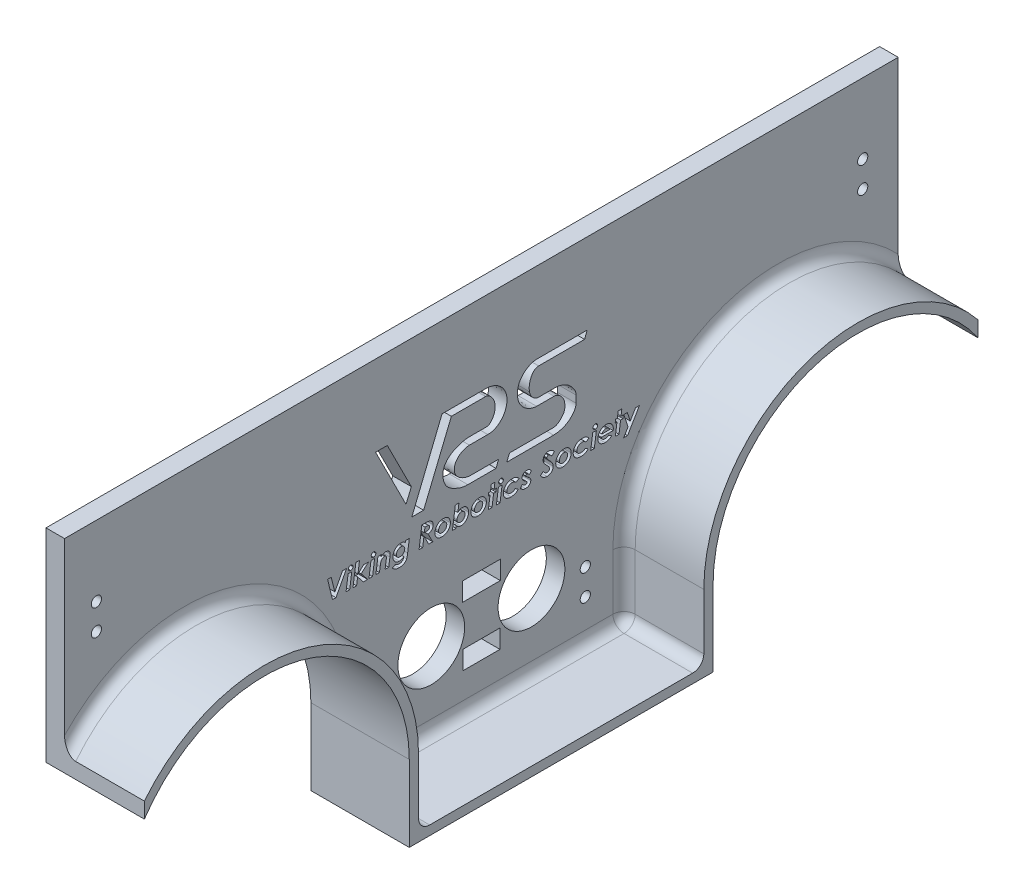
SolidWorks part; units mm, degrees
ref_plane "Front" through (0, 0, 0) normal (0, 0, 1) x (1, 0, 0)
ref_plane "Top" through (0, 0, 0) normal (0, 1, 0) x (1, 0, 0)
ref_plane "Right" through (0, 0, 0) normal (1, 0, 0) x (0, 0, -1)
sketch "wheelArchesSketch" plane through (0, 0, 0) normal (1, 0, 0) x (0, 0, -1)
  line L0 (112.295, 7.5) -> (112.295, 0) construction
  line L1 (0, 0) -> (224.59, 0) construction
  line L2 (0, 0) -> (0, 7.5) construction
  line L3 (0, 7.5) -> (224.59, 7.5) construction
  line L4 (224.59, 0) -> (224.59, 7.5) construction
  line L5 (71.3676, 20.5282) -> (71.3676, 0)
  line L6 (153.2224, 20.5282) -> (153.2224, 0)
  line L7 (73.8676, 20.5282) -> (73.8676, 0)
  line L8 (0, 42.2846) -> (0, 46.5011)
  line L9 (150.7224, 20.5282) -> (150.7224, 0)
  line L10 (224.59, 42.2846) -> (224.59, 46.5011)
  line L12 (150.7224, 0) -> (153.2224, 0)
  line L13 (71.3676, 0) -> (73.8676, 0)
  arc A1 (0, 42.2846) -> (71.3676, 20.5282) centre (32.3676, 20.5282) cw
  arc A2 (224.59, 42.2846) -> (153.2224, 20.5282) centre (192.2224, 20.5282) ccw
  arc A3 (0, 46.5011) -> (73.8676, 20.5282) centre (32.3676, 20.5282) cw
  arc A4 (-2.0748, 43.6792) -> (73.8676, 20.5282) centre (32.3676, 20.5282) cw construction
  arc A5 (224.59, 46.5011) -> (150.7224, 20.5282) centre (192.2224, 20.5282) ccw
  point P5 (32.3676, 20.5282)
  dimension "D5" = 39
  dimension "D1" = 224.59
  dimension "D2" = 7.5
  dimension "D3" = 32.3676
  dimension "D4" = 13.0282
  dimension "D6" = 2.5
extrude "wheelArches" add sketch "wheelArchesSketch" along normal blind 26.5
sketch "Sketch3" plane through (0, 0, 0) normal (1, 0, 0) x (0, 0, -1)
  line L0 (0, 46.5011) -> (0, 42.2846) construction
  line L1 (71.3676, 0) -> (153.2224, 0)
  line L2 (0, 42.2846) -> (0, 87)
  line L3 (0, 87) -> (224.59, 87)
  line L4 (224.59, 42.2846) -> (224.59, 87)
  line L6 (224.59, 42.2846) -> (224.59, 46.5011) construction
  line L7 (71.3676, 0) -> (73.8676, 0) construction
  line L8 (71.3676, 20.5282) -> (71.3676, 0) construction
  line L9 (71.3676, 20.5282) -> (71.3676, 0)
  line L10 (153.2224, 0) -> (153.2224, 20.5282) construction
  line L11 (153.2224, 0) -> (153.2224, 20.5282)
  arc A0 (71.3676, 20.5282) -> (0, 42.2846) centre (32.3676, 20.5282) ccw construction
  arc A1 (71.3676, 20.5282) -> (0, 42.2846) centre (32.3676, 20.5282) ccw
  arc A2 (224.59, 42.2846) -> (153.2224, 20.5282) centre (192.2224, 20.5282) ccw construction
  arc A3 (224.59, 42.2846) -> (153.2224, 20.5282) centre (192.2224, 20.5282) ccw
  dimension "D1" = 87
extrude "sideWall" add sketch "Sketch3" along normal blind 2.5
sketch "Sketch4" plane through (2.5, 0, 0) normal (1, 0, 0) x (0, 0, -1)
  line L0 (150.7224, 0) -> (150.7224, 20.5282) construction
  line L1 (73.8676, 0) -> (150.7224, 0) construction
  line L2 (73.8676, 0) -> (73.8676, 7.5) construction
  line L3 (73.8676, 7.5) -> (150.7224, 7.5) construction
  line L4 (150.7224, 0) -> (150.7224, 7.5) construction
  line L5 (112.295, 7.5) -> (112.295, 37) construction
  line L6 (87.295, 7.5) -> (137.295, 7.5) construction
  line L7 (87.295, 7.5) -> (87.295, 37) construction
  line L8 (87.295, 37) -> (137.295, 37) construction
  line L9 (137.295, 7.5) -> (137.295, 37) construction
  circle A0 centre (98.795, 22.5) radius 9
  circle A1 centre (90.9643, 31.289) radius 0.875
  circle A2 centre (90.9643, 13.711) radius 0.875
  circle A3 centre (133.6257, 13.711) radius 0.875
  circle A4 centre (133.6257, 31.289) radius 0.875
  circle A5 centre (125.795, 22.5) radius 9
  point P11 (112.295, 7.5)
  point P12 (112.295, 7.5)
  dimension "D4" = 18
  dimension "D7" = 1.75
  dimension "D1" = 7.5
  dimension "D2" = 29.5
  dimension "D3" = 50
  dimension "D5" = 5.711
  dimension "D6" = 3.6693
  dimension "D8" = 6.211
  dimension "D9" = 3.6693
  dimension "D10" = 15
  dimension "D11" = 11.5
extrude "distanceSensorMountingHoles1" cut sketch "Sketch4" against normal blind 10
sketch "Sketch5" plane through (2.5, 0, 0) normal (1, 0, 0) x (0, 0, -1)
  circle A0 centre (90.9643, 31.289) radius 1.25
  circle A1 centre (90.9643, 13.711) radius 1.25
  circle A2 centre (133.6257, 13.711) radius 1.25
  circle A3 centre (133.6257, 31.289) radius 1.25
  dimension "D1" = 2.5
extrude "distanceSensorMountingHoles2" cut sketch "Sketch5" against normal offset from surface (1.5 mm away) 1 up to face at (0, 31.289, -90.0893)
sketch "Sketch6" plane through (0, 87, 0) normal (0, 1, 0) x (1, 0, 0)
  line L4 (0, 224.59) -> (0, 0)
  line L5 (0, 0) -> (2.5, 0)
  line L6 (2.5, 0) -> (2.5, 224.59)
  line L7 (2.5, 224.59) -> (0, 224.59)
  line L8 (0, 224.59) -> (0, 0)
  line L9 (0, 0) -> (2.5, 0)
  line L10 (2.5, 0) -> (2.5, 224.59)
  line L11 (2.5, 224.59) -> (0, 224.59)
  dimension "D1" = 0
extrude "wallExtension" add sketch "Sketch6" along normal blind 5
ref_plane "referencePlane1" through (0, 87, 0) normal (0, 1, 0) x (1, 0, 0)
sketch "Sketch7" plane through (0, 87, 0) normal (0, 1, 0) x (1, 0, 0)
  line L0 (0, 112.295) -> (-12.5, 112.295) construction
  line L1 (0, 224.59) -> (0, 0) construction
  line L2 (0, 207.455) -> (-12.5, 207.455)
  line L3 (0, 0) -> (-12.5, 0)
  line L4 (0, 0) -> (0, 17.135)
  line L5 (0, 17.135) -> (-12.5, 17.135)
  line L6 (-12.5, 0) -> (-12.5, 17.135)
  line L7 (-12.5, 224.59) -> (-12.5, 207.455)
  line L8 (0, 224.59) -> (-12.5, 224.59)
  line L9 (0, 224.59) -> (0, 207.455)
  dimension "D1" = 17.135
  dimension "D2" = 12.5
extrude "topChassisMountingTabs" add sketch "Sketch7" against normal blind 5
sketch "Sketch8" plane through (0, 87, 0) normal (0, 1, 0) x (1, 0, 0)
  line L0 (0, 112.295) -> (-12.8293, 112.295) construction
  line L1 (0, 224.59) -> (0, 0) construction
  line L2 (-6.25, 0) -> (-6.25, 17.135) construction
  line L3 (-12.5, 0) -> (0, 0) construction
  line L4 (0, 17.135) -> (-12.5, 17.135) construction
  circle A0 centre (-6.25, 8.5675) radius 1.375
  circle A1 centre (-6.25, 216.0225) radius 1.375
  dimension "D1" = 2.75
extrude "topChassisMountingHoles" cut sketch "Sketch8" against normal blind 5
ref_plane "referencePlane2" through (0, 7.5, 0) normal (0, -1, 0) x (-1, 0, 0)
sketch "Sketch9" plane through (0, 7.5, 0) normal (0, -1, 0) x (-1, 0, 0)
  line L0 (0, 224.59) -> (0, 0) construction
  line L1 (0, 87.295) -> (12.5, 87.295)
  line L2 (0, 87.295) -> (0, 137.295)
  line L3 (0, 137.295) -> (12.5, 137.295)
  line L4 (12.5, 87.295) -> (12.5, 137.295)
  point P4 (0, 112.295)
  point P7 (0, 112.295)
  dimension "D1" = 12.5
  dimension "D2" = 50
extrude "bottomTab" add sketch "Sketch9" against normal blind 1.75
sketch "Sketch10" plane through (0, 9.25, 0) normal (0, 1, 0) x (1, 0, 0)
  line L0 (-12.5, 112.295) -> (0, 112.295) construction
  line L1 (-12.5, 87.295) -> (-12.5, 137.295) construction
  line L2 (0, 137.295) -> (0, 87.295) construction
  line L3 (0, 87.295) -> (-12.5, 87.295) construction
  circle A0 centre (-9.75, 90.295) radius 1.375
  circle A1 centre (-9.75, 134.295) radius 1.375
  dimension "D1" = 2.75
  dimension "D2" = 3
  dimension "D3" = 2.75
extrude "bottomTabMountingHoles" cut sketch "Sketch10" against normal blind 1.75
sketch "Sketch11" plane through (0, 92, 0) normal (0, 1, 0) x (1, 0, 0)
  line L4 (2.5, 224.59) -> (0, 224.59)
  line L5 (0, 224.59) -> (0, 0)
  line L6 (0, 0) -> (2.5, 0)
  line L7 (2.5, 0) -> (2.5, 224.59)
  line L8 (2.5, 224.59) -> (0, 224.59)
  line L9 (0, 224.59) -> (0, 0)
  line L10 (0, 0) -> (2.5, 0)
  line L11 (2.5, 0) -> (2.5, 224.59)
  dimension "D1" = 0
extrude "Boss-Extrude1" add sketch "Sketch11" along normal blind 5
sketch "Sketch12" plane through (2.5, 0, 0) normal (1, 0, 0) x (0, 0, -1)
  line L6 (150.7224, 0) -> (150.7224, 20.5282)
  line L7 (224.59, 46.5011) -> (224.59, 97)
  line L8 (224.59, 97) -> (0, 97)
  line L9 (0, 97) -> (0, 46.5011)
  line L10 (73.8676, 20.5282) -> (73.8676, 0)
  line L11 (73.8676, 0) -> (150.7224, 0)
  line L12 (150.7224, 0) -> (150.7224, 20.5282)
  line L13 (224.59, 46.5011) -> (224.59, 97)
  line L14 (224.59, 97) -> (0, 97)
  line L15 (0, 97) -> (0, 46.5011)
  line L16 (73.8676, 20.5282) -> (73.8676, 0)
  line L17 (73.8676, 0) -> (150.7224, 0)
  circle A0 centre (90.9643, 13.711) radius 0.875 construction
  circle A1 centre (133.6257, 13.711) radius 0.875 construction
  arc A2 (224.59, 46.5011) -> (150.7224, 20.5282) centre (192.2224, 20.5282) ccw
  arc A3 (73.8676, 20.5282) -> (0, 46.5011) centre (32.3676, 20.5282) ccw
  arc A4 (224.59, 46.5011) -> (150.7224, 20.5282) centre (192.2224, 20.5282) ccw
  arc A5 (73.8676, 20.5282) -> (0, 46.5011) centre (32.3676, 20.5282) ccw
  circle A6 centre (133.6257, 31.289) radius 0.875 construction
  circle A7 centre (90.9643, 31.289) radius 0.875 construction
  circle A8 centre (90.9643, 13.711) radius 0.875
  circle A9 centre (133.6257, 13.711) radius 0.875
  circle A10 centre (133.6257, 31.289) radius 0.875
  circle A11 centre (90.9643, 31.289) radius 0.875
  dimension "D1" = 0
extrude "Boss-Extrude2" add sketch "Sketch12" along normal blind 2.5
sketch "Sketch13" plane through (1, 0, 0) normal (1, 0, 0) x (0, 0, -1)
  circle A0 centre (90.9643, 31.289) radius 1.25 construction
  circle A1 centre (90.9643, 31.289) radius 1.25
  circle A2 centre (133.6257, 13.711) radius 1.25 construction
  circle A3 centre (133.6257, 13.711) radius 1.25
  circle A4 centre (90.9643, 13.711) radius 1.25 construction
  circle A5 centre (90.9643, 13.711) radius 1.25
  circle A6 centre (133.6257, 31.289) radius 1.25 construction
  circle A7 centre (133.6257, 31.289) radius 1.25
extrude "Cut-Extrude1" cut sketch "Sketch13" along normal through all
sketch "Sketch14" plane through (2.5, 0, 0) normal (-1, 0, 0) x (0, 0, 1)
  circle A1 centre (-125.795, 22.5) radius 9
  circle A2 centre (-125.795, 22.5) radius 9
  circle A3 centre (-98.795, 22.5) radius 9
  circle A4 centre (-98.795, 22.5) radius 9
  dimension "D1" = 0
  dimension "D2" = 0
extrude "Cut-Extrude2" cut sketch "Sketch14" against normal blind 10
sketch "Sketch15" plane through (5, 0, 0) normal (1, 0, 0) x (0, 0, -1)
  line L0 (98.795, 13.5) -> (98.795, 31.5) construction
  line L1 (89.795, 22.5) -> (107.795, 22.5) construction
  line L3 (107.295, 17.5) -> (117.295, 17.5)
  line L4 (107.295, 17.5) -> (107.295, 12.5)
  line L5 (107.295, 12.5) -> (117.295, 12.5)
  line L6 (117.295, 17.5) -> (117.295, 12.5)
  line L7 (107.185, 33.5) -> (117.405, 33.5)
  line L8 (107.185, 33.5) -> (107.185, 28.5)
  line L9 (107.185, 28.5) -> (117.405, 28.5)
  line L10 (117.405, 33.5) -> (117.405, 28.5)
  circle A0 centre (98.795, 22.5) radius 9 construction
  circle A1 centre (98.795, 22.5) radius 9 construction
  point P24 (107.185, 31)
  dimension "D1" = 5
  dimension "D2" = 10
  dimension "D3" = 8.5
  dimension "D4" = 5
  dimension "D5" = 5
  dimension "D6" = 10.22
  dimension "D7" = 8.39
  dimension "D8" = 8.5
extrude "Cut-Extrude3" cut sketch "Sketch15" against normal blind 10
sketch "Sketch16" plane through (0, 87, 0) normal (0, 1, 0) x (1, 0, 0)
  line L0 (0, 224.59) -> (0, 0) construction
  line L1 (-12.5, 0) -> (0, 0)
  line L2 (-12.5, 0) -> (-12.5, 2)
  line L3 (-12.5, 2) -> (0, 2)
  line L4 (0, 0) -> (0, 2)
  dimension "D1" = 2
extrude "Cut-Extrude4" cut sketch "Sketch16" against normal blind 10
sketch "Sketch17" plane through (5, 0, 0) normal (1, 0, 0) x (0, 0, -1)
  line L0 (150.7224, 20.5282) -> (150.7224, 0) construction
  line L1 (73.8676, 0) -> (150.7224, 0)
  line L2 (73.8676, 0) -> (73.8676, 2.5)
  line L3 (73.8676, 2.5) -> (150.7224, 2.5)
  line L4 (150.7224, 0) -> (150.7224, 2.5)
  dimension "D1" = 2.5
extrude "Boss-Extrude3" add sketch "Sketch17" along normal up to surface (21.5 mm away) up to face at (26.5, 30.4055, -51.2877)
fillet "Fillet1" radius 3 7 edges at (5, 11.5141, -150.7224) (5, 11.5141, -73.8676) (5, 59.6786, -178.4566) (5, 2.5, -112.295) (5, 59.6786, -46.1334) (15.75, 2.5, -150.7224) (15.75, 2.5, -73.8676)
sketch "Sketch18" plane through (0, 0, 0) normal (-1, 0, 0) x (0, 0, 1)
  line L0 (-112.295, 0) -> (-112.295, 97) construction
  line L6 (-224.59, 51.0665) -> (-224.59, 97) construction
  line L11 (-71.3676, 0) -> (-153.2224, 0) construction
  line L12 (-224.59, 97) -> (0, 97) construction
  line L13 (0, 97) -> (0, 51.0665) construction
  line L14 (-206.455, 82.0153) -> (-223.59, 82.0153) construction
  line L15 (-206.455, 82.0153) -> (-206.455, 67.0153) construction
  line L16 (-206.455, 67.0153) -> (-223.59, 67.0153) construction
  line L17 (-223.59, 82.0153) -> (-223.59, 67.0153) construction
  circle A6 centre (-215.0225, 78.0153) radius 1.375
  circle A7 centre (-215.0225, 71.0153) radius 1.375
  circle A12 centre (-8.5675, 78.0153) radius 1.375
  circle A13 centre (-8.5675, 71.0153) radius 1.375
  point P11 (-215.0225, 82.0153)
  dimension "D2" = 1
  dimension "D7" = 4
  dimension "D5" = 2.75
  dimension "D3" = 15
  dimension "D4" = 18.9847
  dimension "D6" = 7
  dimension "D8" = 8.5675
  dimension "D11" = 9.5675
extrude "Cut-Extrude5" cut sketch "Sketch18" against normal blind 10
sketch "Sketch19" plane through (0, 87, 0) normal (0, 1, 0) x (1, 0, 0)
  line L1 (-12.5, 17.135) -> (0, 17.135)
  line L2 (-12.5, 17.135) -> (-12.5, 2)
  line L3 (-12.5, 2) -> (0, 2)
  line L4 (0, 17.135) -> (0, 2)
  line L5 (-12.5, 224.59) -> (0, 224.59)
  line L6 (-12.5, 224.59) -> (-12.5, 207.455)
  line L7 (-12.5, 207.455) -> (0, 207.455)
  line L8 (0, 224.59) -> (0, 207.455)
extrude "Cut-Extrude6" cut sketch "Sketch19" against normal blind 10
sketch "Sketch20" plane through (0, 0, 0) normal (-1, 0, 0) x (0, 0, 1)
  line L0 (-112.295, 9.25) -> (-112.295, 33.5) construction
  line L1 (-137.295, 9.25) -> (-87.295, 9.25) construction
  line L2 (-107.185, 33.5) -> (-117.405, 33.5) construction
  circle A0 centre (-140.295, 20.25) radius 1.375
  circle A1 centre (-140.295, 13.25) radius 1.375
  circle A2 centre (-84.295, 13.25) radius 1.375
  circle A3 centre (-84.295, 20.25) radius 1.375
  dimension "D1" = 2.75
  dimension "D2" = 7
  dimension "D3" = 3
  dimension "D4" = 4
extrude "Cut-Extrude7" cut sketch "Sketch20" against normal blind 10
sketch "Sketch21" plane through (0, 9.25, 0) normal (0, 1, 0) x (1, 0, 0)
  line L4 (0, 87.295) -> (0, 137.295)
  line L5 (0, 137.295) -> (-12.5, 137.295)
  line L6 (-12.5, 137.295) -> (-12.5, 87.295)
  line L7 (-12.5, 87.295) -> (0, 87.295)
  line L8 (0, 87.295) -> (0, 137.295)
  line L9 (0, 137.295) -> (-12.5, 137.295)
  line L10 (-12.5, 137.295) -> (-12.5, 87.295)
  line L11 (-12.5, 87.295) -> (0, 87.295)
  dimension "D1" = 0
extrude "Cut-Extrude8" cut sketch "Sketch21" against normal blind 10
sketch "Sketch22" plane through (5, 0, 0) normal (1, 0, 0) x (0, 0, -1)
  circle A0 centre (90.9643, 31.289) radius 1.25
  circle A1 centre (90.9643, 13.711) radius 1.25
  circle A2 centre (133.6257, 13.711) radius 1.25
  circle A3 centre (133.6257, 31.289) radius 1.25
  circle A5 centre (90.9643, 31.289) radius 1.25 construction
  circle A6 centre (90.9643, 13.711) radius 1.25 construction
  circle A7 centre (133.6257, 31.289) radius 1.25 construction
  circle A8 centre (133.6257, 13.711) radius 1.25 construction
extrude "Boss-Extrude4" add sketch "Sketch22" against normal up to surface (5 mm away) up to face at (0, 46.5599, -112.295)
sketch "Sketch24" plane through (5, 0, 0) normal (1, 0, 0) x (0, 0, -1)
  line L0 (147.5058, 113.6649) -> (400.1724, 113.6649) construction
sketch "vrs logo sketch 1" plane through (5, 0, 0) normal (1, 0, 0) x (0, 0, -1)
  line L0 (83.795, 75.25) -> (91.9924, 58.9987)
  line L1 (83.795, 55.25) -> (140.795, 55.25) construction
  line L2 (83.795, 55.25) -> (83.795, 75.25) construction
  line L3 (83.795, 75.25) -> (140.795, 75.25) construction
  line L4 (140.795, 55.25) -> (140.795, 75.25) construction
  line L5 (91.9924, 58.9987) -> (93.4297, 62.4001)
  line L6 (93.4297, 62.4001) -> (86.948, 75.25)
  line L7 (83.795, 75.25) -> (86.948, 75.25)
  line L8 (93.5622, 55.25) -> (101.6971, 75.25)
  line L9 (93.5622, 55.25) -> (96.7347, 55.25)
  line L10 (96.7347, 55.25) -> (104.2097, 73.4229)
  line L11 (104.2097, 73.4229) -> (113.4267, 73.4229)
  line L12 (101.6971, 75.25) -> (113.4267, 75.25)
  line L14 (113.6549, 66.2225) -> (109.0786, 66.2225)
  line L15 (108.649, 55.25) -> (116.2406, 55.25)
  line L16 (116.2406, 55.25) -> (116.9169, 57.0415)
  line L17 (116.9169, 57.0415) -> (109.3254, 57.0415)
  line L18 (109.0786, 64.2665) -> (114.0207, 64.2665)
  line L19 (119.112, 55.25) -> (119.8911, 57.0415)
  line L20 (119.8911, 57.0415) -> (131.7476, 57.0415)
  line L21 (119.112, 55.25) -> (131.7476, 55.25)
  line L22 (127.1813, 64.2665) -> (131.882, 64.2665)
  line L23 (137.7903, 59.7038) -> (137.7903, 61.5921)
  line L24 (131.882, 66.1231) -> (127.6113, 66.1231)
  line L25 (127.1813, 75.25) -> (140.795, 75.25)
  line L26 (140.795, 75.25) -> (140.1067, 73.4229)
  line L27 (140.1067, 73.4229) -> (127.7258, 73.4229)
  line L28 (224.59, 97) -> (0, 97) construction
  line L29 (112.295, 33.5) -> (112.295, 97) construction
  line L30 (117.405, 33.5) -> (107.185, 33.5) construction
  spline S0 degree 3 poles (113.4267, 73.4229) (113.9525, 73.4229) (115.0028, 72.7273) (116.0805, 70.9166) (116.0595, 68.7609) (115.3054, 67.2973) (114.5742, 66.4875) (113.9987, 66.2225) (113.6549, 66.2225) knots 0 0 0 0 0.157632 0.37711 0.656481 0.801127 0.898936 1 1 1 1
  spline S1 degree 3 poles (131.7476, 57.0415) (132.4242, 57.0415) (133.7383, 57.9339) (134.7873, 59.3816) (134.8085, 60.9137) (134.634, 62.1622) (133.709, 63.5128) (132.6421, 64.2665) (131.882, 64.2665) knots 0 0 0 0 0.216224 0.409178 0.515063 0.662579 0.774486 1 1 1 1
  spline S2 degree 3 poles (109.0786, 66.2225) (108.231, 66.2225) (106.3717, 65.827) (103.9189, 64.7653) (102.071, 62.8032) (101.7499, 60.0852) (102.7398, 57.4648) (104.9299, 56.1868) (106.7888, 55.4161) (108.037, 55.25) (108.649, 55.25) knots 0 0 0 0 0.134192 0.283292 0.411281 0.526526 0.689263 0.809142 0.905564 1 1 1 1
  spline S3 degree 3 poles (109.3254, 57.0415) (107.7745, 57.0815) (104.9095, 58.4278) (104.9721, 62.7864) (107.5033, 64.2156) (109.0786, 64.2665) knots 0 0 0 0 0.430007 0.587207 1 1 1 1
  spline S4 degree 3 poles (114.0207, 64.2665) (116.5078, 64.2354) (119.3744, 67.0337) (119.1976, 71.6207) (117.1158, 74.4983) (114.7913, 75.25) (113.4267, 75.25) knots 0 0 0 0 0.405476 0.592612 0.768817 1 1 1 1
  spline S5 degree 3 poles (131.7476, 55.25) (132.7169, 55.3021) (134.3226, 55.5397) (136.1797, 56.7261) (137.3685, 58.0352) (137.7903, 59.1283) (137.7903, 59.7038) knots 0 0 0 0 0.36059 0.578347 0.799146 1 1 1 1
  spline S6 degree 3 poles (137.7903, 61.5921) (137.7903, 61.8737) (137.6589, 62.6634) (136.8588, 63.8882) (135.6659, 65.0851) (134.1983, 65.8074) (133.2186, 66.0284) (132.7609, 66.0839) knots 0 0 0 0 0.113 0.331746 0.588751 0.807468 1 1 1 1
  spline S7 degree 3 poles (132.7609, 66.0839) (132.4698, 66.1192) (132.177, 66.1231) (131.882, 66.1231) knots 0 0 0 0 1 1 1 1
  spline S8 degree 3 poles (127.1813, 64.2665) (126.7197, 64.2665) (125.617, 64.5125) (124.2158, 65.2204) (122.9183, 66.5025) (122.3334, 67.5228) (122.1993, 68.257) knots 0 0 0 0 0.20352 0.489339 0.680254 1 1 1 1
  spline S9 degree 3 poles (127.6113, 66.1231) (127.3676, 66.1231) (126.867, 66.2987) (126.21, 66.7226) (125.5853, 67.4936) (125.3454, 68.1893) (125.2705, 68.6229) knots 0 0 0 0 0.204924 0.409427 0.639806 1 1 1 1
  spline S10 degree 3 poles (122.1993, 68.257) (121.9161, 69.4274) (121.9261, 71.4717) (123.3759, 73.5449) (124.7544, 74.5858) (126.0309, 75.125) (126.8446, 75.25) (127.1813, 75.25) knots 0 0 0 0 0.373666 0.579957 0.752029 0.896516 1 1 1 1
  spline S11 degree 3 poles (125.2705, 68.6229) (125.1123, 69.4156) (125.1861, 70.7682) (125.8714, 72.2737) (126.68, 73.2015) (127.3274, 73.4229) (127.7258, 73.4229) knots 0 0 0 0 0.404345 0.656951 0.820838 1 1 1 1
  point P86 (112.295, 97)
  point P88 (112.295, 75.25)
  point P96 (112.295, 65.25)
  point P97 (83.795, 65.25)
  dimension "D11" = 1.7915
  dimension "D1" = 57
  dimension "D2" = 20
  dimension "D3" = 3.7487
  dimension "D4" = 8.1974
  dimension "D5" = 1.4373
  dimension "D6" = 3.4014
  dimension "D7" = 3.1725
  dimension "D8" = 9.7672
  dimension "D9" = 17.9021
  dimension "D10" = 1.8271
  dimension "D12" = 24.854
  dimension "D13" = 3.2018
  dimension "D14" = 1.8271
  dimension "D15" = 1.9798
  dimension "D16" = 1.6669
  dimension "D17" = 5.1584
  dimension "D18" = 2.2337
  dimension "D19" = 0.9169
  dimension "D20" = 0.2396
  dimension "D21" = 2.587
  dimension "D22" = 0.0819
  dimension "D23" = 1.9243
  dimension "D24" = 1.2106
  dimension "D25" = 7.5916
  dimension "D26" = 7.5915
  dimension "D27" = 1.915
  dimension "D28" = 2.5794
  dimension "D29" = 1.1838
  dimension "D30" = 1.8883
  dimension "D31" = 2.217
  dimension "D32" = 0.3308
  dimension "D33" = 1.8913
  dimension "D34" = 1.6187
  dimension "D35" = 1.2558
  dimension "D36" = 2.614
  dimension "D37" = 1.7701
  dimension "D38" = 1.3617
  dimension "D39" = 2.571
  dimension "D40" = 0.4501
  dimension "D41" = 2.571
  dimension "D42" = 0.9042
  dimension "D43" = 4.5763
  dimension "D44" = 4.9421
  dimension "D45" = 0.8895
  dimension "D46" = 0.322
  dimension "D47" = 3.3748
  dimension "D48" = 1.3467
  dimension "D49" = 0.66
  dimension "D50" = 0.6344
  dimension "D51" = 2.7967
  dimension "D52" = 1.6292
  dimension "D53" = 1.2054
  dimension "D54" = 0.6164
  dimension "D55" = 0.145
  dimension "D56" = 3.1675
  dimension "D57" = 0.0254
  dimension "D58" = 2.6147
  dimension "D59" = 1.0653
  dimension "D60" = 1.7565
  dimension "D61" = 1.7394
  dimension "D62" = 2.4266
  dimension "D63" = 1.3285
  dimension "D64" = 9.217
  dimension "D65" = 1.9536
  dimension "D66" = 12.6356
  dimension "D67" = 11.8565
  dimension "D68" = 1.2782
  dimension "D69" = 0.1355
  dimension "D70" = 1.5916
  dimension "D71" = 0.4543
  dimension "D72" = 1.9312
  dimension "D73" = 1.0151
  dimension "D74" = 1.5049
  dimension "D75" = 0.9426
  dimension "D76" = 1.038
  dimension "D77" = 1.6472
  dimension "D78" = 1.1839
  dimension "D79" = 1.3566
  dimension "D80" = 0.0665
  dimension "D81" = 1.0663
  dimension "D82" = 0.4841
  dimension "D83" = 1.5648
  dimension "D84" = 1.4607
  dimension "D85" = 0.2862
  dimension "D86" = 1.8883
  dimension "D87" = 0.1266
  dimension "D88" = 0.808
  dimension "D89" = 0.9451
  dimension "D90" = 0.6179
  dimension "D91" = 1.3726
  dimension "D92" = 0.7891
  dimension "D93" = 1.9971
  dimension "D94" = 1.0905
  dimension "D95" = 1.2891
  dimension "D96" = 1.341
  dimension "D97" = 0.7106
  dimension "D98" = 1.4145
  dimension "D99" = 0.3115
  dimension "D100" = 1.3582
  dimension "D101" = 0.0391
  dimension "D102" = 0.8789
  dimension "D103" = 4.7007
  dimension "D104" = 4.2707
  dimension "D105" = 21.683
  dimension "D106" = 1.3625
  dimension "D107" = 0.2502
  dimension "D108" = 0.7247
  dimension "D109" = 0.1998
  dimension "D110" = 1.7247
  dimension "D111" = 0.9
  dimension "D112" = 0.4122
  dimension "D113" = 0.6268
  dimension "D114" = 0.9314
  dimension "D115" = 0.9061
  dimension "D116" = 0.6514
  dimension "D117" = 0.5384
  dimension "D118" = 1.2933
  dimension "D119" = 0.505
  dimension "D120" = 0.7628
  dimension "D121" = 0.3384
  dimension "D122" = 1.4102
  dimension "D123" = 0.1889
  dimension "D124" = 0.1124
  dimension "D125" = 0.4736
  dimension "D126" = 0.093
  dimension "D127" = 1.0443
  dimension "D128" = 0.3786
  dimension "D129" = 2.2095
  dimension "D130" = 0.2054
  dimension "D131" = 1.3574
  dimension "D132" = 1.6763
  dimension "D133" = 1.1326
  dimension "D134" = 0.6426
  dimension "D135" = 1.3694
  dimension "D136" = 1.0215
  dimension "D137" = 1.3432
  dimension "D138" = 0.5374
  dimension "D139" = 1.3111
  dimension "D140" = 0.6752
  dimension "D141" = 0.7122
  dimension "D142" = 1.0054
  dimension "D143" = 0.138
  dimension "D144" = 1.0251
  dimension "D145" = 0.3166
  dimension "D146" = 13.6137
  dimension "D147" = 12.3809
  dimension "D148" = 28.5
extrude "Cut-Extrude9" cut sketch "vrs logo sketch 1" against normal through all both and the other way through all
sketch "Sketch25" plane through (5, 0, 0) normal (1, 0, 0) x (0, 0, -1)
  line L0 (112.295, 33.5) -> (112.295, 97) construction
  line L1 (224.59, 97) -> (0, 97) construction
  line L3 (70.5049, 46.6488) -> (154.0851, 46.6488) construction
  text T0 "Viking Robotics Society" font "Century Gothic" height 5.4
  point P8 (112.295, 46.6488)
  point P13 (112.295, 46.6488)
extrude "Cut-Extrude10" cut sketch "Sketch25" against normal blind 2.5
